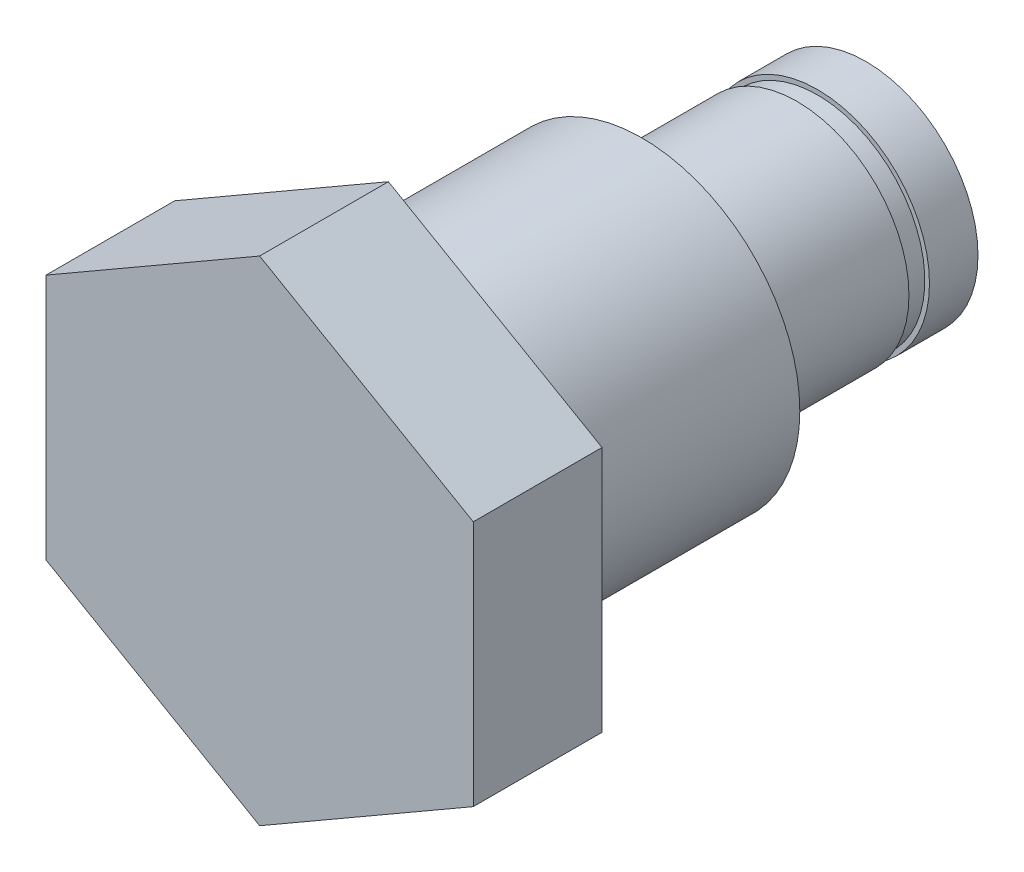
SolidWorks part; units mm, degrees
material "PLA"
ref_plane "Front Plane" through (0, 0, 0) normal (0, 0, 1) x (1, 0, 0)
ref_plane "Top Plane" through (0, 0, 0) normal (0, 1, 0) x (1, 0, 0)
ref_plane "Right Plane" through (0, 0, 0) normal (1, 0, 0) x (0, 0, -1)
sketch "Sketch1" plane through (0, 0, 0) normal (0, 0, 1) x (1, 0, 0)
  circle A0 centre (0, 0) radius 8.45
  dimension "D1" = 16.9
extrude "Boss-Extrude1" add sketch "Sketch1" against normal blind 13.6
sketch "Sketch2" plane through (0, 0, 0) normal (0, 0, 1) x (1, 0, 0)
  line L0 (0, -13.2213) -> (0, 13.2213) construction
  line L1 (0, 13.2213) -> (-11.45, 6.6107)
  line L2 (-11.45, 6.6107) -> (-11.45, -6.6107)
  line L3 (-11.45, -6.6107) -> (0, -13.2213)
  line L4 (0, -13.2213) -> (11.45, -6.6107)
  line L5 (11.45, -6.6107) -> (11.45, 6.6107)
  line L6 (11.45, 6.6107) -> (0, 13.2213)
  circle A1 centre (0, 0) radius 11.45 construction
  dimension "D1" = 22.9
extrude "Boss-Extrude2" add sketch "Sketch2" along normal blind 6.9
ref_axis "Axis1" through (0, 0, -13.6) along (0, 0, 1)
sketch "Sketch3" plane through (0, 0, -13.6) normal (0, 0, -1) x (-1, 0, 0)
  circle A0 centre (0, 0) radius 6
  dimension "D1" = 12
extrude "Boss-Extrude3" add sketch "Sketch3" along normal blind 12
ref_plane "Plane1" through (0, 0, -21.9) normal (0, 0, -1) x (-1, 0, 0)
sketch "Sketch5" plane through (0, 0, -21.9) normal (0, 0, -1) x (-1, 0, 0)
  circle A0 centre (0, 0) radius 5.75
  circle A1 centre (0, 0) radius 6
  dimension "D1" = 12
  dimension "D2" = 11.5
extrude "Cut-Extrude1" cut sketch "Sketch5" along normal blind 1.1
